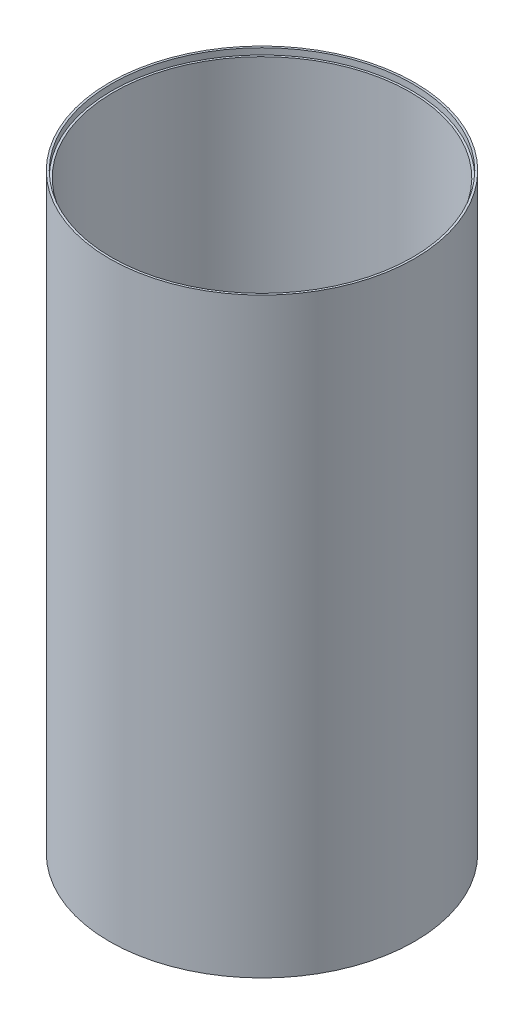
SolidWorks part; units mm, degrees
material "Silica Phenolic"
ref_plane "Piano frontale" through (0, 0, 0) normal (0, 0, 1) x (1, 0, 0)
ref_plane "Piano superiore" through (0, 0, 0) normal (0, 1, 0) x (1, 0, 0)
ref_plane "Piano destro" through (0, 0, 0) normal (1, 0, 0) x (0, 0, -1)
sketch "Schizzo1" plane through (0, 0, 0) normal (0, 0, 1) x (1, 0, 0)
  line L0 (0, 0) -> (0, 21.1255) construction
  line L1 (-72, 0) -> (-72, 3)
  line L2 (-72, 3) -> (-71, 3)
  line L3 (-71, 3) -> (-71, 280)
  line L4 (-71, 280) -> (-72, 280)
  line L5 (-72, 280) -> (-72, 283)
  line L6 (-72, 283) -> (-73, 283)
  line L7 (-73, 283) -> (-73, 0)
  line L8 (-73, 0) -> (-72, 0)
  dimension "D1" = 2
  dimension "D2" = 142
  dimension "D3" = 3
  dimension "D4" = 283
  dimension "D5" = 3
revolve "Rivoluzione1" add sketch "Schizzo1" angle 360 about L0
